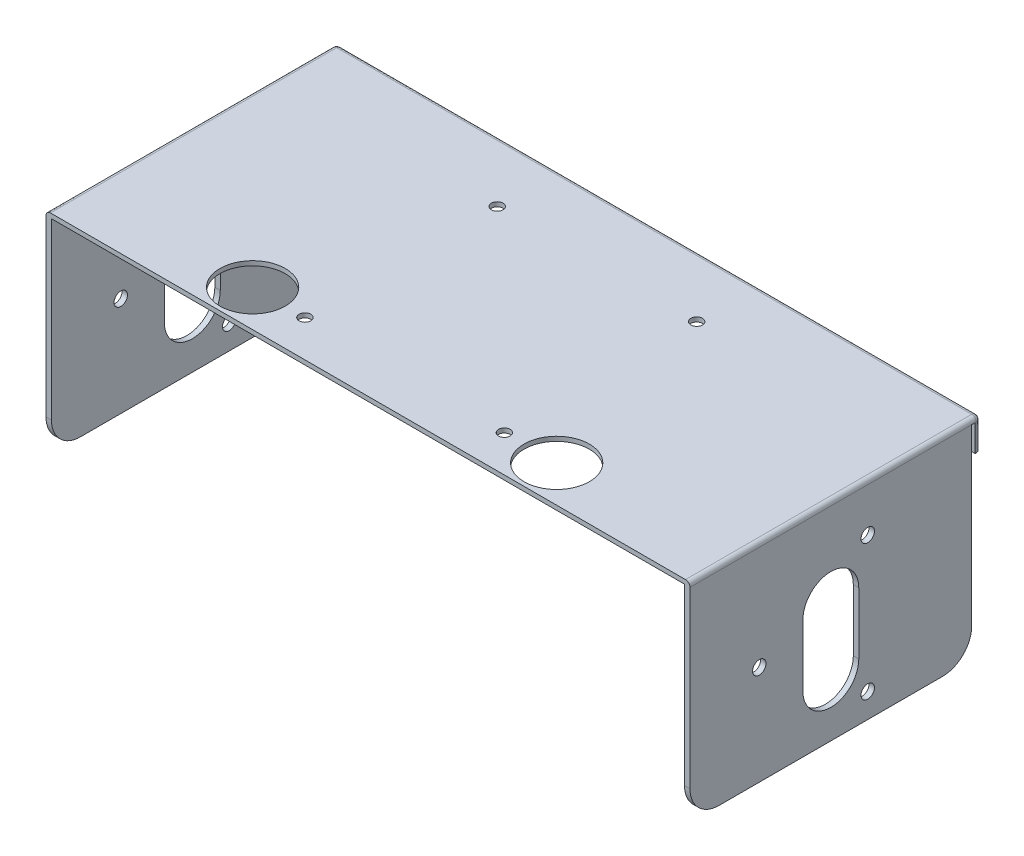
SolidWorks part; units mm, degrees
ref_plane "Plan de face" through (0, 0, 0) normal (0, 0, 1) x (1, 0, 0)
ref_plane "Plan de dessus" through (0, 0, 0) normal (0, 1, 0) x (1, 0, 0)
ref_plane "Plan de droite" through (0, 0, 0) normal (1, 0, 0) x (0, 0, -1)
sketch "Esquisse2" plane through (0, 0, 0) normal (0, 1, 0) x (1, 0, 0)
  line L0 (-72, 0) -> (72, 0)
  line L1 (-72, 0) -> (-72, 65)
  line L2 (-72, 65) -> (72, 65)
  line L3 (72, 65) -> (72, 0)
  point P3 (0, 0)
  dimension "D1" = 144
  dimension "D2" = 65
extrude "Boss.-Extru.1" add sketch "Esquisse2" along normal blind 1
sketch "Esquisse3" plane through (0, 0, 0) normal (0, -1, 0) x (1, 0, 0)
  line L0 (-72, -65) -> (-72, -63.78)
  line L1 (72, -65) -> (-72, -65) construction
  line L2 (-72, -63.78) -> (72, -63.78)
  line L3 (72, -63.78) -> (72, -65)
  line L6 (-72, -65) -> (72, -65)
  line L7 (-72, -65) -> (-72, 0) construction
  line L8 (72, 0) -> (72, -65) construction
  dimension "D1" = 1.22
extrude "Boss.-Extru.2" add sketch "Esquisse3" along normal blind 6
sketch "Esquisse6" plane through (0, 0, 0) normal (0, -1, 0) x (-1, 0, 0)
  line L0 (70.78, 0) -> (70.78, 63)
  line L1 (72, 0) -> (-72, 0) construction
  line L2 (70.78, 63) -> (72, 63)
  line L3 (72, 63.78) -> (72, 0) construction
  line L4 (72, 63) -> (72, 0)
  line L5 (72, 0) -> (70.78, 0)
  line L6 (-72, 0) -> (-72, 63)
  line L7 (-72, 0) -> (-72, 63.78) construction
  line L8 (-72, 63) -> (-70.78, 63)
  line L9 (-70.78, 63) -> (-70.78, 0)
  line L10 (-70.78, 0) -> (-72, 0)
  line L11 (72, 65) -> (-72, 65) construction
  dimension "D1" = 2
  dimension "D2" = 2
  dimension "D3" = 1.22
  dimension "D4" = 1.22
extrude "Boss.-Extru.4" add sketch "Esquisse6" along normal blind 45.5
fillet "Congé3" radius 1 1 edges at (0, 1, -65)
fillet "Congé4" radius 1 6 edges at (-72, -3, -65) (-72, 0.7071, -64.7071) (72, -3, -65) (72, 0.7071, -64.7071) (-72, 1, -32) (72, 1, -32)
sketch "Esquisse7" plane through (72, 0, 0) normal (1, 0, 0) x (0, 0, -1)
  line L0 (0, -45.5) -> (0, -39)
  line L1 (0, 0) -> (0, -45.5) construction
  line L2 (0, -45.5) -> (6.5, -45.5)
  line L3 (63, -45.5) -> (0, -45.5) construction
  line L4 (56.5, -45.5) -> (63, -45.5)
  line L5 (63, -45.5) -> (63, -39)
  line L6 (63, -45.5) -> (63, 0) construction
  arc A0 (0, -39) -> (6.5, -45.5) centre (6.5, -39) ccw
  arc A1 (63, -39) -> (56.5, -45.5) centre (56.5, -39) cw
  dimension "D1" = 6.5
  dimension "D2" = 6.5
extrude "Enlèv. mat.-Extru.2" cut sketch "Esquisse7" against normal through all
sketch "Esquisse8" plane through (0, 1, 0) normal (0, 1, 0) x (1, 0, 0)
  line L0 (-71, 64) -> (-71, 0) construction
  line L1 (71, 0) -> (71, 64) construction
  line L2 (-71, 0) -> (71, 0) construction
  circle A0 centre (-34, 8.2) radius 7.3
  circle A1 centre (34, 8.2) radius 7.3
  dimension "D3" = 14.6
  dimension "D4" = 8.2
  dimension "D1" = 37
  dimension "D2" = 37
extrude "Enlèv. mat.-Extru.3" cut sketch "Esquisse8" against normal through all
sketch "Esquisse9" plane through (0, 1, 0) normal (0, 1, 0) x (1, 0, 0)
  line L0 (-22.3, 51.2) -> (22.3, 51.2) construction
  line L1 (-71, 0) -> (71, 0) construction
  circle A0 centre (-22.3, 8.2) radius 1.3
  circle A1 centre (22.3, 8.2) radius 1.3
  circle A2 centre (-34, 8.2) radius 7.3 construction
  circle A3 centre (34, 8.2) radius 7.3 construction
  circle A4 centre (-22.3, 51.2) radius 1.3
  circle A5 centre (22.3, 51.2) radius 1.3
  dimension "D3" = 8.2
  dimension "D1" = 11.7
  dimension "D2" = 11.7
  dimension "D4" = 43
extrude "Enlèv. mat.-Extru.4" cut sketch "Esquisse9" against normal through all
sketch "Esquisse10" plane through (72, 0, 0) normal (1, 0, 0) x (0, 0, -1)
  line L0 (31.5, -32.75) -> (31.5, -18.95) construction
  line L1 (25.25, -32.75) -> (25.25, -18.95)
  line L2 (37.75, -32.75) -> (37.75, -18.95)
  line L4 (56.5, -45.5) -> (6.5, -45.5) construction
  line L5 (0, 1) -> (64, 1) construction
  arc A0 (25.25, -32.75) -> (37.75, -32.75) centre (31.5, -32.75) ccw
  arc A1 (37.75, -18.95) -> (25.25, -18.95) centre (31.5, -18.95) ccw
  point P2 (31.5, -25.85)
  point P9 (31.5, -45.5)
  point P10 (31.5, -12.7)
  point P11 (31.5, -39)
  dimension "D4" = 13.7
  dimension "D1" = 12.5
  dimension "D2" = 12.5
  dimension "D3" = 26.3
extrude "Enlèv. mat.-Extru.6" cut sketch "Esquisse10" against normal through all
sketch "Esquisse11" plane through (72, 0, 0) normal (1, 0, 0) x (0, 0, -1)
  line L0 (0, 0) -> (0, -39) construction
  line L1 (63, -39) -> (63, 0) construction
  line L2 (56.5, -45.5) -> (6.5, -45.5) construction
  line L3 (0, 1) -> (64, 1) construction
  circle A0 centre (39.75, -40.05) radius 1.5
  circle A1 centre (39.75, -9.75) radius 1.5
  circle A2 centre (15.5, -23.25) radius 1.5
  point P14 (0, 0)
  point P15 (0, 0)
  dimension "D2" = 3
  dimension "D4" = 3
  dimension "D7" = 3
  dimension "D1" = 5.45
  dimension "D3" = 23.25
  dimension "D5" = 10.75
  dimension "D6" = 24.25
  dimension "D8" = 15.5
extrude "Enlèv. mat.-Extru.7" cut sketch "Esquisse11" against normal through all
